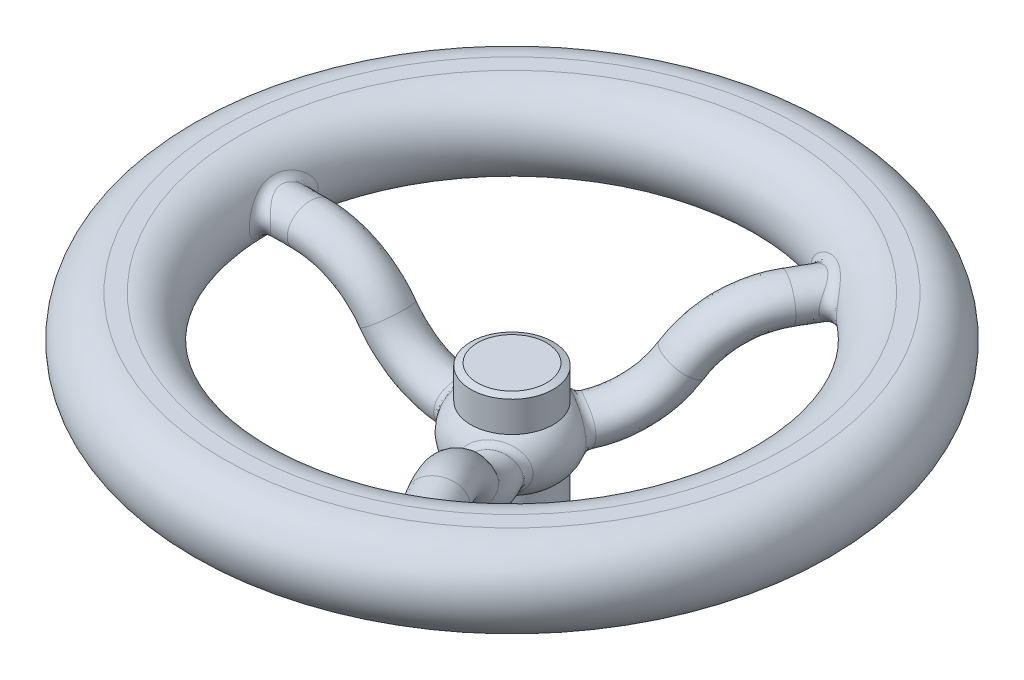
SolidWorks part; units mm, degrees
material "Aluminum Bronze"
ref_plane "Front Plane" through (0, 0, 0) normal (0, 0, 1) x (1, 0, 0)
ref_plane "Top Plane" through (0, 0, 0) normal (0, 1, 0) x (1, 0, 0)
ref_plane "Right Plane" through (0, 0, 0) normal (1, 0, 0) x (0, 0, -1)
sketch "Sketch1" plane through (0, 0, 0) normal (0, 0, 1) x (1, 0, 0)
  line L0 (0, 0) -> (0, 45) construction
  line L1 (0, 45) -> (-12.5, 45)
  line L2 (-12.5, 45) -> (-12.5, 35)
  line L3 (-12.5, 0) -> (0, 0)
  line L4 (-12.5, 19) -> (-12.5, 0)
  line L5 (0, 0) -> (0, 45)
  arc A0 (-12.5, 35) -> (-12.5, 19) centre (-6.5, 27) ccw
  point P9 (-16.5, 27)
  dimension "D1" = 4
  dimension "D2" = 10
  dimension "D3" = 16
  dimension "D4" = 45
  dimension "D5" = 25
revolve "Revolve1" add sketch "Sketch1" angle 360 about L0
sketch "Sketch2" plane through (0, 0, 0) normal (0, 0, 1) x (1, 0, 0)
  line L0 (-87.5, 51) -> (-82.5, 51) construction
  line L1 (-87.5, 63.5) -> (-82.5, 63.5)
  line L2 (-87.5, 38.5) -> (-82.5, 38.5)
  line L3 (0, 0) -> (0, 64.1038) construction
  line L4 (12.5, 45) -> (-12.5, 45) construction
  arc A0 (-87.5, 63.5) -> (-87.5, 38.5) centre (-87.5, 51) ccw
  arc A1 (-82.5, 38.5) -> (-82.5, 63.5) centre (-82.5, 51) ccw
  point P2 (-85, 51)
  point P10 (-70, 51)
  point P11 (-100, 51)
  dimension "D1" = 30
  dimension "D2" = 25
  dimension "D3" = 6
  dimension "D4" = 170
revolve "Revolve4" add sketch "Sketch2" angle 360 about L3
sketch "Sketch3" plane through (0, 0, 0) normal (0, 0, 1) x (1, 0, 0)
  line L0 (0, 27) -> (-14.1698, 27)
  line L2 (-61.1591, 51) -> (-85, 51)
  arc A0 (-14.1698, 27) -> (-37.6644, 39) centre (-14.1698, 56) cw
  arc A1 (-37.6644, 39) -> (-61.1591, 51) centre (-61.1591, 22) ccw
  dimension "D2" = 29
  dimension "D1" = 70.8302
sketch "Sketch9" plane through (0, 0, 0) normal (1, 0, 0) x (0, 0, -1)
  line L0 (0, 39) -> (0, 27) construction
  ellipse E0 centre (0, 27) end of major axis (7, 27) minor radius 6
  dimension "D1" = 14
  dimension "D2" = 12
sweep "Sweep2" add profiles "Sketch9" path "Sketch3"
pattern_circular "CirPattern2" count 3 over 360 of "Sweep2"
fillet "Fillet1" radius 3 4 edges at (1.4811, 27.9665, -16.3864) (40.8812, 50.6945, 56.8265) (13.4505, 27.9665, 9.4758) (28.7726, 50.6945, -63.8174)
fillet "Fillet2" radius 3 2 edges at (-69.6538, 51.3055, 6.9909) (-14.9316, 27.9665, 6.9106)
chamfer "Chamfer2" distance 2 angle 20 1 edges at (0, 45, -12.5) first distance on face at (0, 45, -12.5)
sketch "Sketch11" plane through (0, 0, 0) normal (0, -1, 0) x (1, 0, 0)
  line L0 (-4.8567, 6.432) -> (-4.2852, -6.826)
  arc A0 (-4.2852, -6.826) -> (-4.8567, 6.432) centre (0, 0) ccw
extrude "Cut-Extrude1" cut sketch "Sketch11" against normal blind 10
equation "\"thik\"= 25"
equation "\"A\"= 110"
equation "\"B\"= 80"
equation "\"C35\"= 35"
equation "\"diam\"=25"
equation "\"D5@Sketch1\"=\"diam\""
equation "\"R\"= \"diam\" / 2"
equation "\"D2@Sketch2\"=\"diam\""
